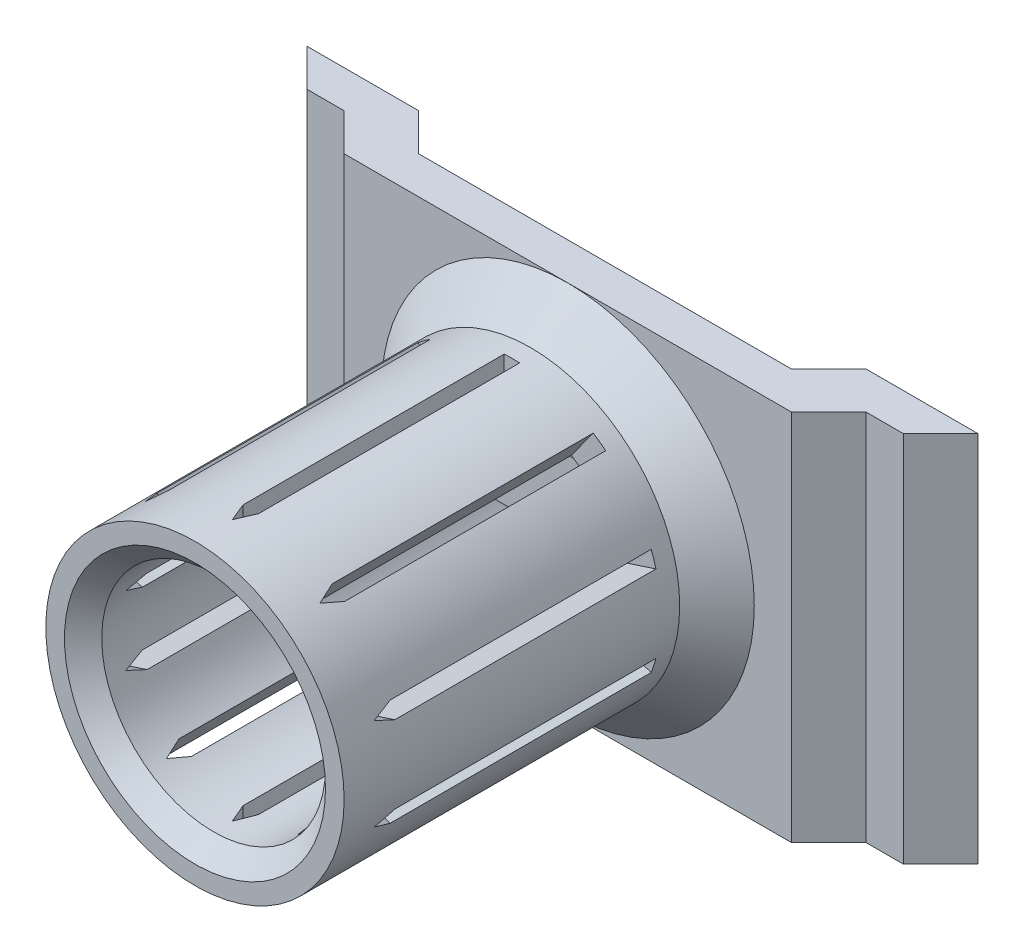
SolidWorks part; units mm, degrees
ref_plane "Plan de face" through (0, 0, 0) normal (0, 0, 1) x (1, 0, 0)
ref_plane "Plan de dessus" through (0, 0, 0) normal (0, 1, 0) x (1, 0, 0)
ref_plane "Plan de droite" through (0, 0, 0) normal (1, 0, 0) x (0, 0, -1)
sketch "Esquisse1" plane through (0, 0, 0) normal (0, 0, 1) x (1, 0, 0)
  line L1 (-5, 5) -> (5, 5)
  line L2 (-5, 5) -> (-5, -5)
  line L3 (-5, -5) -> (5, -5)
  line L4 (5, 5) -> (5, -5)
  line L5 (-5, 5) -> (5, -5) construction
  line L6 (-5, -5) -> (5, 5) construction
  line L7 (-2.8284, 1) -> (2.8284, 1)
  line L9 (-2.8284, -1) -> (2.8284, -1)
  line L11 (-2.8284, 1) -> (2.8284, -1) construction
  line L12 (-2.8284, -1) -> (2.8284, 1) construction
  line L13 (-5, -5) -> (-6, -5)
  line L14 (-5, -5) -> (-5, 5)
  line L15 (-5, 5) -> (-6, 5)
  line L16 (-6, -5) -> (-6, 5)
  line L17 (5, -5) -> (6, -5)
  line L18 (5, -5) -> (5, 5)
  line L19 (5, 5) -> (6, 5)
  line L20 (6, -5) -> (6, 5)
  circle A0 centre (0, 0) radius 3
  circle A1 centre (0, 0) radius 4
  point P0 (0, 0)
  point P19 (2.922, 0.6798)
  point P20 (-2.9046, -0.7504)
  dimension "D1" = 6
  dimension "D4" = 1
  dimension "D2" = 10
  dimension "D3" = 10
  dimension "D5" = 2
  dimension "D6" = 1
  dimension "D7" = 1
extrude "Boss.-Extru.1" add sketch "Esquisse1" along normal blind 1 contours L4 L1 L2 L3 A1 | A1 A0 | L7 A0 L9 | L16 L13 L2 L15 | L17 L20 L19 L4
sketch "Esquisse2" plane through (0, 0, 1) normal (0, 0, 1) x (1, 0, 0)
  circle A0 centre (0, 0) radius 3
  circle A1 centre (0, 0) radius 4
  arc M2 (-2.8284, 1) -> (2.8284, 1) centre (0, 0) cw
  arc M9 (2.8284, -1) -> (-2.8284, -1) centre (0, 0) cw
  dimension "D1" = 1
  dimension "D2" = 6
extrude "Boss.-Extru.2" add sketch "Esquisse2" along normal blind 10 contours A1 A0 M2 M9
chamfer "Chanfrein1" distance 1 angle 45 1 edges at (4, 0, 1)
sketch3d "Esquisse3D1" plane through (0, 0, 0) normal (0, 0, 1) x (1, 0, 0)
sketch "Esquisse3" plane through (0, 0, 0) normal (0, 1, 0) x (1, 0, 0)
  line L2 (0, -2) -> (0, -11) construction
  line L3 (4, -2) -> (-4, -2) construction
  line L4 (-0.2062, -3.4978) -> (0.2062, -3.4978)
  line L5 (-0.2062, -3.4978) -> (-0.2062, -9.5022)
  line L6 (-0.2062, -9.5022) -> (0.2062, -9.5022)
  line L7 (0.2062, -3.4978) -> (0.2062, -9.5022)
  line L8 (-0.2062, -3.4978) -> (0.2062, -9.5022) construction
  line L9 (-0.2062, -9.5022) -> (0.2062, -3.4978) construction
  line L10 (-0.2062, -3.4978) -> (0.2062, -3.4978)
  line L11 (-4, -11) -> (4, -11) construction
  line L12 (0, -6.5) -> (1.2358, -6.5) construction
  line L13 (0, -10) -> (0.2062, -9.5022)
  line L14 (-0.2062, -9.5022) -> (0, -10)
  line L15 (-0.2062, -3.4978) -> (-0.2062, -2.5)
  line L16 (-0.2062, -2.5) -> (0.2062, -2.5)
  line L17 (0.2062, -3.4978) -> (0.2062, -2.5)
  point P0 (0, -6.5)
  dimension "D1" = 0.5
  dimension "D2" = 1
extrude "Enlèv. mat.-Extru.1" cut sketch "Esquisse3" along normal up to surface (3.9947 mm away)
pattern_circular "Répétition circulaire1" count 10 over 360 about axis through (0, 0, 0) along (0, 0, 1) of "Enlèv. mat.-Extru.1"
sketch "Esquisse9" plane through (0, 0, 0) normal (0, 0, -1) x (-1, 0, 0)
  line L0 (5, 5) -> (-5, 5) construction
  line L1 (-5, -5) -> (-9, -5)
  line L2 (-5, -5) -> (-5, 5)
  line L3 (-5, 5) -> (-9, 5)
  line L4 (-9, -5) -> (-9, 5)
  line L5 (0, 0) -> (0, 0.8729) construction
  line L6 (5, 5) -> (9, 5)
  line L7 (9, -5) -> (9, 5)
  line L8 (5, -5) -> (9, -5)
  line L9 (5, -5) -> (5, 5)
  line M12 (-6, -5) -> (6, -5)
  line M13 (6, -5) -> (6, 5)
  line M14 (6, 5) -> (-6, 5)
  line M15 (-6, 5) -> (-6, -5)
  dimension "D1" = 4
extrude "Boss.-Extru.8" add sketch "Esquisse9" along normal blind 1 contours L4 L1 L3 M15 | L8 L7 L6 M13 | L9 M12 M13 M14
chamfer "Chanfrein2" distance 1 angle 45 6 edges at (6, 0, 0) (5, 0, -1) (-6, 0, 0) (-5, 0, -1) (-9, 0, 0) (9, 0, 0)
chamfer "Chanfrein3" distance 0.5 angle 45 1 edges at (3, 0, 11)
